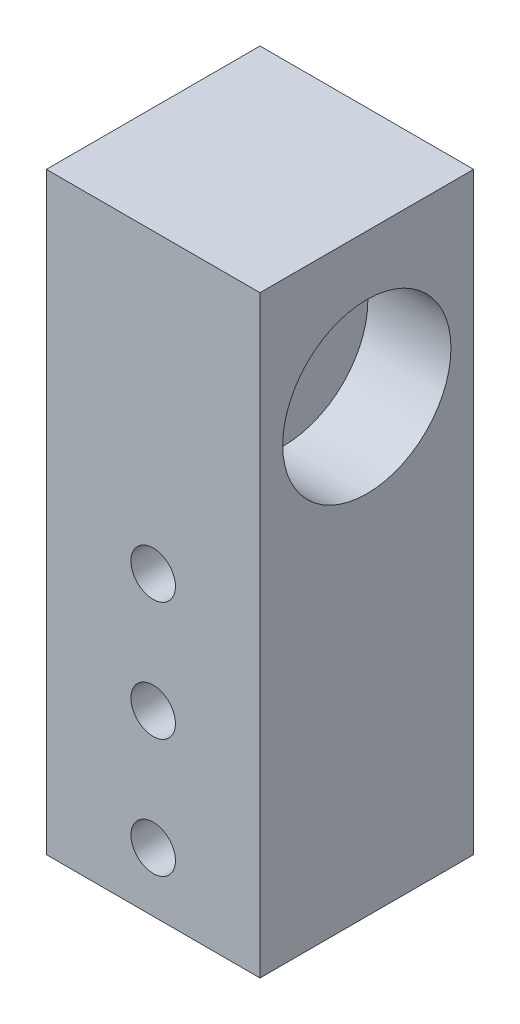
SolidWorks part; units mm, degrees
ref_plane "Front Plane" through (0, 0, 0) normal (0, 0, 1) x (1, 0, 0)
ref_plane "Top Plane" through (0, 0, 0) normal (0, 1, 0) x (1, 0, 0)
ref_plane "Right Plane" through (0, 0, 0) normal (1, 0, 0) x (0, 0, -1)
sketch "Sketch1" plane through (0, 0, 0) normal (0, 0, 1) x (1, 0, 0)
  line L1 (0, 0) -> (45.72, 0)
  line L2 (0, 0) -> (0, 76.2)
  line L3 (0, 76.2) -> (45.72, 76.2)
  line L4 (45.72, 0) -> (45.72, 76.2)
  dimension "D1" = 76.2
  dimension "D2" = 45.72
extrude "Boss-Extrude1" add sketch "Sketch1" along normal mid plane 45.72
sketch "Sketch2" plane through (0, 0, 22.86) normal (0, 0, 1) x (1, 0, 0)
  line L0 (0, 0) -> (45.72, 0) construction
  line L1 (45.72, 76.2) -> (0, 76.2) construction
  line L2 (0, 76.2) -> (0, 0) construction
  circle A0 centre (22.86, 12.7) radius 4.7625
  circle A1 centre (22.86, 38.1) radius 4.7625
  circle A2 centre (22.86, 63.5) radius 4.7625
  dimension "D1" = 9.525
  dimension "D2" = 22.86
  dimension "0.25" = 9.525
  dimension "D3" = 9.525
  dimension "D4" = 25.4
  dimension "D5" = 25.4
  dimension "D6" = 12.7
  dimension "D7" = 12.7
extrude "Cut-Extrude1" cut sketch "Sketch2" against normal through all
sketch "Sketch3" plane through (0, 76.2, 0) normal (0, 1, 0) x (1, 0, 0)
  line L1 (0, 22.86) -> (45.72, 22.86)
  line L2 (0, 22.86) -> (0, -22.86)
  line L3 (0, -22.86) -> (45.72, -22.86)
  line L4 (45.72, 22.86) -> (45.72, -22.86)
extrude "Boss-Extrude2" add sketch "Sketch3" along normal blind 50.8
sketch "Sketch4" plane through (45.72, 0, 0) normal (1, 0, 0) x (0, 0, -1)
  line L0 (-22.86, 127) -> (22.86, 127) construction
  circle A0 centre (0, 96.3) radius 18
  dimension "D1" = 35.9999
  dimension "D2" = 30.7
extrude "Cut-Extrude2" cut sketch "Sketch4" against normal blind 17.78
sketch "Sketch5" plane through (27.94, 0, 0) normal (1, 0, 0) x (0, 0, -1)
  circle A0 centre (0, 96.3) radius 3
extrude "Cut-Extrude3" cut sketch "Sketch5" against normal through all
